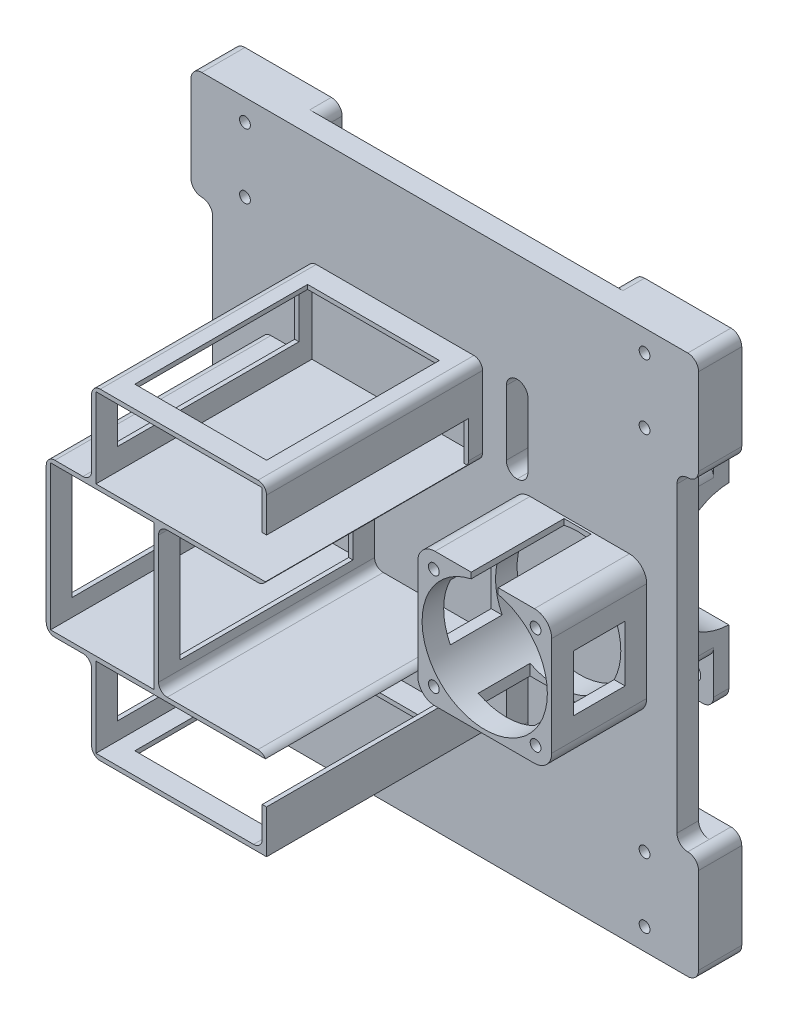
SolidWorks part; units mm, degrees
other "Marquage1"
sketch "Esquisse17" plane through (0, -52.2, -65) normal (-0.4358, -0.0146, -0.8999) x (-0.2736, 0.9547, 0.117)
ref_plane "Plan de face" through (0, 0, 0) normal (0, 0, 1) x (1, 0, 0)
ref_plane "Plan de dessus" through (0, 0, 0) normal (0, 1, 0) x (1, 0, 0)
ref_plane "Plan de droite" through (0, 0, 0) normal (1, 0, 0) x (0, 0, -1)
sketch "Esquisse1" plane through (0, 0, 0) normal (0, 0, 1) x (1, 0, 0)
  line L5 (235, 50) -> (235, 0)
  line L7 (0, 50) -> (0, 0)
  line L9 (235, 200) -> (235, 250)
  line L11 (0, 250) -> (0, 200)
  line L16 (225, 200) -> (225, 50)
  line L19 (146, 50) -> (156, 50)
  line L20 (225, 50) -> (235, 50)
  line L21 (225, 200) -> (235, 200)
  line L23 (10, 200) -> (10, 50)
  line L24 (0, 200) -> (10, 200)
  line L27 (10, 50) -> (0, 50)
  line L32 (0, 250) -> (235, 250)
  line L33 (0, 0) -> (235, 0)
  line L35 (146, 200) -> (156, 200)
  line L36 (146, 160) -> (156, 160)
  line L37 (146, 90) -> (156, 90)
  line L38 (146, 200) -> (146, 160)
  line L39 (156, 200) -> (156, 160)
  line L40 (146, 90) -> (146, 50)
  line L41 (156, 90) -> (156, 50)
  circle A0 centre (117.5, 125) radius 0.005
  dimension "D19" = 0.01
  dimension "D1" = 50
  dimension "D2" = 235
  dimension "D11" = 10
  dimension "D12" = 10
  dimension "D15" = 10
  dimension "D16" = 10
  dimension "D17" = 150
  dimension "D18" = 50
  dimension "D6" = 235
  dimension "D21" = 125
  dimension "D20" = 117.5
  dimension "D7" = 50
  dimension "D8" = 40
  dimension "D9" = 40
  dimension "D13" = 10
  dimension "D14" = 10
  dimension "D3" = 79
  dimension "D10" = 79
  dimension "D5" = 35
  dimension "D4" = 35
extrude "Boss.-Extru.2" add sketch "Esquisse1" along normal blind 10
sketch "Esquisse4" plane through (0, 0, 0) normal (0, 0, -1) x (-1, 0, 0)
  line L0 (0, 250) -> (0, 200) construction
  line L1 (0, 250) -> (-50, 250)
  line L2 (0, 250) -> (0, 200)
  line L4 (-50, 250) -> (-50, 200)
  line L5 (-117.5, 250) -> (-117.5, 0) construction
  line L6 (0, 0) -> (-235, 0) construction
  line L7 (-235, 200) -> (-185, 200)
  line L8 (-235, 250) -> (-235, 200)
  line L9 (-185, 250) -> (-185, 200)
  line L10 (-235, 250) -> (-185, 250)
  line L11 (-225, 125) -> (-10, 125) construction
  line L12 (-225, 50) -> (-225, 200) construction
  line L21 (-10, 200) -> (-10, 50) construction
  line L22 (0, 200) -> (-50, 200)
  line L24 (-235, 250) -> (0, 250) construction
  line L25 (0, 250) -> (0, 200) construction
  line L26 (-235, 50) -> (-185, 50)
  line L27 (-185, 0) -> (-185, 50)
  line L28 (-235, 0) -> (-235, 50)
  line L29 (-235, 0) -> (-185, 0)
  line L30 (0, 50) -> (-50, 50)
  line L31 (0, 0) -> (0, 50)
  line L32 (-50, 0) -> (-50, 50)
  line L33 (0, 0) -> (-50, 0)
  dimension "D1" = 50
  dimension "D2" = 50
extrude "Boss.-Extru.3" add sketch "Esquisse4" along normal blind 10
sketch "Esquisse6" plane through (0, 0, 0) normal (0, 0, -1) x (-1, 0, 0)
  line L0 (-225, 50) -> (-225, 200) construction
  line L1 (-126, 164) -> (-106, 164)
  line L2 (-126, 164) -> (-126, 86)
  line L3 (-126, 86) -> (-106, 86)
  line L4 (-106, 164) -> (-106, 86)
  line L5 (-146, 90) -> (-146, 50) construction
  line L6 (-50, 200) -> (0, 200) construction
  line L7 (-10, 50) -> (-50, 50) construction
  line L10 (-225, 200) -> (-185, 200) construction
  line L11 (-195, 164) -> (-175, 164)
  line L12 (-195, 164) -> (-195, 86)
  line L13 (-195, 86) -> (-175, 86)
  line L14 (-175, 164) -> (-175, 86)
  line L15 (-185, 50) -> (-225, 50) construction
  dimension "D5" = 36
  dimension "D6" = 36
  dimension "D1" = 20
  dimension "D8" = 30
  dimension "D3" = 36
  dimension "D4" = 36
  dimension "D7" = 50
  dimension "D2" = 20
extrude "Boss.-Extru.5" add sketch "Esquisse6" along normal blind 45
fillet "Congé1" radius 5 28 edges at (50, 250, -5) (50, 200, -5) (185, 250, -5) (185, 200, -5) (235, 50, 0) (235, 200, 0) (0, 50, 0) (0, 200, 0) (225, 50, 5) (225, 200, 5) (10, 50, 5) (10, 200, 5) (235, 250, 0) (0, 250, 0) (0, 0, 0) (235, 0, 0) (50, 50, -5) (185, 50, -5) (185, 0, -5) (50, 0, -5) (146, 50, 5) (156, 50, 5) (156, 90, 5) (146, 90, 5) (156, 160, 5) (146, 160, 5) (156, 200, 5) (146, 200, 5)
sketch "Esquisse8" plane through (195, 0, 0) normal (1, 0, 0) x (0, 0, -1)
  line L0 (22.5, 164) -> (22.5, 86) construction
  line L2 (45, 125) -> (-10, 125) construction
  line L3 (45, 164) -> (45, 86) construction
  line L4 (0, 164) -> (0, 86) construction
  line L5 (-10, 55) -> (-10, 195) construction
  line L6 (45, 164) -> (0, 164) construction
  line L7 (45, 86) -> (0, 86) construction
  circle A0 centre (45, 125) radius 28.5
  dimension "D1" = 45
  dimension "D2" = 57
extrude "Enlèv. mat.-Extru.2" cut sketch "Esquisse8" against normal blind 100
sketch "Esquisse12" plane through (0, 164, 0) normal (0, 1, 0) x (1, 0, 0)
  line L10 (126, 45) -> (126, 0) construction
  line L11 (106, 45) -> (126, 45)
  line L12 (106, 45) -> (106, 37)
  line L13 (106, 37) -> (126, 37)
  line L14 (126, 45) -> (126, 37)
  line L15 (195, 45) -> (195, 0) construction
  line L16 (175, 45) -> (195, 45)
  line L17 (175, 45) -> (175, 37)
  line L18 (175, 37) -> (195, 37)
  line L19 (195, 45) -> (195, 37)
  dimension "D1" = 8
  dimension "D2" = 8
extrude "Boss.-Extru.6" add sketch "Esquisse12" along normal blind 20
sketch "Esquisse13" plane through (0, 86, 0) normal (0, -1, 0) x (1, 0, 0)
  line L0 (126, -45) -> (126, 0) construction
  line L1 (106, -45) -> (126, -45)
  line L2 (106, -45) -> (106, -37)
  line L3 (106, -37) -> (126, -37)
  line L4 (126, -45) -> (126, -37)
  line L5 (195, -45) -> (195, 0) construction
  line L6 (175, -45) -> (195, -45)
  line L7 (175, -45) -> (175, -37)
  line L8 (175, -37) -> (195, -37)
  line L9 (195, -45) -> (195, -37)
  dimension "D1" = 8
  dimension "D2" = 8
extrude "Boss.-Extru.7" add sketch "Esquisse13" along normal blind 20
fillet "Congé55" radius 5 16 edges at (106, 184, -41) (175, 184, -41) (175, 66, -41) (106, 66, -41) (126, 66, -41) (195, 66, -41) (175, 164, -18.5) (195, 164, -18.5) (126, 164, -18.5) (106, 164, -18.5) (106, 86, -18.5) (126, 86, -18.5) (175, 86, -18.5) (195, 86, -18.5) (195, 184, -41) (126, 184, -41)
sketch "Esquisse14" plane through (0, 0, -45) normal (0, 0, -1) x (-1, 0, 0)
  line L0 (-175, 153.5) -> (-126, 153.5) construction
  line L1 (-150.5, 153.5) -> (-150.5, 184.1356) construction
  line L2 (-175, 153.5) -> (-175, 179) construction
  line L3 (-195, 125) -> (-106, 125) construction
  line L4 (-195, 159) -> (-195, 91) construction
  line L5 (-106, 91) -> (-106, 159) construction
  circle A0 centre (-185, 173.5) radius 4
  circle A1 centre (-116, 173.5) radius 4
  circle A2 centre (-116, 76.5) radius 4
  circle A3 centre (-185, 76.5) radius 4
  dimension "D1" = 8
  dimension "D2" = 20
  dimension "D3" = 10
extrude "Enlèv. mat.-Extru.4" cut sketch "Esquisse14" against normal blind 10
sketch "Esquisse15" plane through (0, 66, 0) normal (0, -1, 0) x (1, 0, 0)
  line L5 (195, -37) -> (195, -45) construction
  line L6 (175, -45) -> (195, -45)
  line L7 (175, -45) -> (175, -44)
  line L8 (175, -44) -> (195, -44)
  line L9 (195, -45) -> (195, -44)
  dimension "D1" = 1
extrude "Enlèv. mat.-Extru.5" cut sketch "Esquisse15" against normal blind 120
sketch "Esquisse19" plane through (0, 0, 10) normal (0, 0, 1) x (1, 0, 0)
  line L0 (117.5, 250) -> (117.5, -7.5909) construction
  line L1 (230, 250) -> (5, 250) construction
  line L2 (225, 125) -> (-27.1362, 125) construction
  line L3 (225, 55) -> (225, 195) construction
  line L5 (156, 165) -> (156, 195) construction
  line L6 (149, 94) -> (211, 94)
  line L7 (149, 94) -> (149, 156)
  line L8 (149, 156) -> (211, 156)
  line L9 (211, 94) -> (211, 156)
  line L10 (149, 94) -> (211, 156) construction
  line L11 (149, 156) -> (211, 94) construction
  line L12 (160, 105) -> (200, 105)
  line L13 (160, 105) -> (160, 145)
  line L14 (160, 145) -> (200, 145)
  line L15 (200, 105) -> (200, 145)
  line L16 (160, 105) -> (200, 145) construction
  line L17 (160, 145) -> (200, 105) construction
  point P8 (180, 125)
  point P11 (180, 125)
  dimension "D2" = 40
  dimension "D3" = 0
  dimension "D6" = 0
  dimension "D1" = 24
  dimension "D4" = 62
  dimension "D5" = 62
extrude "Boss.-Extru.8" add sketch "Esquisse19" along normal blind 44
sketch "Esquisse20" plane through (0, 0, 54) normal (0, 0, 1) x (1, 0, 0)
  line L0 (117.5, 250) -> (117.5, 0) construction
  line L1 (230, 250) -> (5, 250) construction
  line L2 (5, 0) -> (230, 0) construction
  line L3 (10, 125) -> (225, 125) construction
  line L4 (10, 195) -> (10, 55) construction
  line L5 (225, 55) -> (225, 195) construction
  line L6 (149, 156) -> (149, 94) construction
  circle A0 centre (180, 125) radius 29
  circle A1 centre (180, 125) radius 15
  point P12 (180, 125)
  dimension "D2" = 58
  dimension "D3" = 30
  dimension "D1" = 31
extrude "Enlèv. mat.-Extru.7" cut sketch "Esquisse20" against normal blind 44
fillet "Congé57" radius 8 4 edges at (211, 94, 32) (211, 156, 32) (149, 156, 32) (149, 94, 32)
sketch "Esquisse21" plane through (0, 0, 54) normal (0, 0, 1) x (1, 0, 0)
  line L0 (149, 148) -> (149, 102) construction
  line L1 (173.75, 158) -> (186.25, 158)
  line L2 (173.75, 158) -> (173.75, 152)
  line L3 (173.75, 152) -> (186.25, 152)
  line L4 (186.25, 158) -> (186.25, 152)
  line L7 (203, 156) -> (157, 156) construction
  point P6 (149, 125)
  point P9 (180, 156)
  dimension "D2" = 6
  dimension "D3" = 33
  dimension "D1" = 6.25
  dimension "D4" = 12.5
extrude "Enlèv. mat.-Extru.8" cut sketch "Esquisse21" against normal blind 43
sketch "Esquisse22" plane through (0, 0, 0) normal (0, 0, 1) x (1, 0, 0)
  line L0 (117.5, 250) -> (117.5, 0) construction
  line L1 (230, 250) -> (5, 250) construction
  line L2 (5, 0) -> (230, 0) construction
  line L3 (117.5, 0) -> (225, 125) construction
  line L4 (225, 55) -> (225, 195) construction
  line L5 (225, 125) -> (10, 125) construction
  line L6 (10, 195) -> (10, 55) construction
  line L7 (12.5, 240) -> (37.5, 240) construction
  line L8 (12.5, 245) -> (37.5, 245)
  line L9 (12.5, 235) -> (37.5, 235)
  line L10 (12.5, 210) -> (37.5, 210) construction
  line L11 (12.5, 215) -> (37.5, 215)
  line L12 (12.5, 205) -> (37.5, 205)
  line L13 (0, 245) -> (0, 205) construction
  line L16 (5, 200) -> (55.9669, 200) construction
  line L19 (12.5, 40) -> (37.5, 40) construction
  line L20 (12.5, 35) -> (37.5, 35)
  line L21 (12.5, 45) -> (37.5, 45)
  line L22 (12.5, 10) -> (37.5, 10) construction
  line L23 (12.5, 5) -> (37.5, 5)
  line L24 (12.5, 15) -> (37.5, 15)
  line L25 (222.5, 10) -> (197.5, 10) construction
  line L26 (222.5, 5) -> (197.5, 5)
  line L27 (222.5, 15) -> (197.5, 15)
  line L28 (222.5, 40) -> (197.5, 40) construction
  line L29 (222.5, 35) -> (197.5, 35)
  line L30 (222.5, 45) -> (197.5, 45)
  line L31 (222.5, 240) -> (197.5, 240) construction
  line L32 (222.5, 245) -> (197.5, 245)
  line L33 (222.5, 235) -> (197.5, 235)
  line L34 (222.5, 210) -> (197.5, 210) construction
  line L35 (222.5, 215) -> (197.5, 215)
  line L36 (222.5, 205) -> (197.5, 205)
  arc A0 (12.5, 245) -> (12.5, 235) centre (12.5, 240) ccw
  arc A1 (37.5, 235) -> (37.5, 245) centre (37.5, 240) ccw
  arc A2 (12.5, 215) -> (12.5, 205) centre (12.5, 210) ccw
  arc A3 (37.5, 205) -> (37.5, 215) centre (37.5, 210) ccw
  arc A8 (12.5, 35) -> (12.5, 45) centre (12.5, 40) cw
  arc A9 (37.5, 45) -> (37.5, 35) centre (37.5, 40) cw
  arc A10 (12.5, 5) -> (12.5, 15) centre (12.5, 10) cw
  arc A11 (37.5, 15) -> (37.5, 5) centre (37.5, 10) cw
  arc A12 (222.5, 5) -> (222.5, 15) centre (222.5, 10) ccw
  arc A13 (197.5, 15) -> (197.5, 5) centre (197.5, 10) ccw
  arc A14 (222.5, 35) -> (222.5, 45) centre (222.5, 40) ccw
  arc A15 (197.5, 45) -> (197.5, 35) centre (197.5, 40) ccw
  arc A16 (222.5, 245) -> (222.5, 235) centre (222.5, 240) cw
  arc A17 (197.5, 235) -> (197.5, 245) centre (197.5, 240) cw
  arc A18 (222.5, 215) -> (222.5, 205) centre (222.5, 210) cw
  arc A19 (197.5, 205) -> (197.5, 215) centre (197.5, 210) cw
  point P14 (25, 240)
  point P19 (25, 210)
  point P32 (25, 40)
  point P39 (25, 10)
  point P47 (210, 10)
  point P54 (210, 40)
  point P61 (210, 240)
  point P68 (210, 210)
  dimension "D3" = 5
  dimension "D4" = 5
  dimension "D1" = 25
  dimension "D2" = 25
  dimension "D5" = 25
  dimension "D6" = 25
  dimension "D7" = 10
  dimension "D8" = 10
extrude "Enlèv. mat.-Extru.9" cut sketch "Esquisse22" against normal blind 10
sketch "Esquisse23" plane through (0, 0, 0) normal (0, 0, 1) x (1, 0, 0)
  line L0 (117.5, 250) -> (117.5, 0) construction
  line L1 (230, 250) -> (5, 250) construction
  line L2 (5, 0) -> (230, 0) construction
  line L3 (117.5, 0) -> (225, 125) construction
  line L4 (225, 55) -> (225, 195) construction
  line L5 (225, 125) -> (10, 125) construction
  line L6 (10, 195) -> (10, 55) construction
  line L7 (0, 245) -> (0, 205) construction
  line L8 (5, 200) -> (40.2929, 200) construction
  circle A0 centre (25, 240) radius 2.5
  circle A1 centre (25, 210) radius 2.5
  circle A3 centre (25, 40) radius 2.5
  circle A4 centre (25, 10) radius 2.5
  circle A5 centre (210, 10) radius 2.5
  circle A6 centre (210, 40) radius 2.5
  circle A7 centre (210, 210) radius 2.5
  circle A8 centre (210, 240) radius 2.5
  dimension "D1" = 25
  dimension "D2" = 10
  dimension "D3" = 25
  dimension "D4" = 10
  dimension "D5" = 5
  dimension "D6" = 5
extrude "Enlèv. mat.-Extru.10" cut sketch "Esquisse23" along normal blind 10
sketch "Esquisse24" plane through (149, 0, 0) normal (-1, 0, 0) x (0, 0, 1)
  line L1 (20, 138) -> (44, 138)
  line L2 (20, 138) -> (20, 112)
  line L3 (20, 112) -> (44, 112)
  line L4 (44, 138) -> (44, 112)
  line L6 (54, 148) -> (54, 102) construction
  line L7 (10, 195) -> (10, 55) construction
  line L8 (54, 148) -> (10, 148) construction
  line L10 (10, 102) -> (54, 102) construction
  dimension "D3" = 10
  dimension "D4" = 10
  dimension "D1" = 10
  dimension "D2" = 10
extrude "Enlèv. mat.-Extru.11" cut sketch "Esquisse24" against normal mid plane 132
sketch "Esquisse25" plane through (0, 94, 0) normal (0, -1, 0) x (1, 0, 0)
  line L0 (157, 54) -> (203, 54) construction
  line L1 (167, 44) -> (193, 44)
  line L2 (167, 44) -> (167, 20)
  line L3 (167, 20) -> (193, 20)
  line L4 (193, 44) -> (193, 20)
  line L5 (203, 10) -> (203, 54) construction
  line L6 (157, 10) -> (203, 10) construction
  line L7 (157, 54) -> (157, 10) construction
  dimension "D1" = 10
  dimension "D2" = 10
  dimension "D3" = 10
  dimension "D4" = 10
extrude "Enlèv. mat.-Extru.12" cut sketch "Esquisse25" against normal blind 42
sketch "Esquisse27" plane through (0, 0, 10) normal (0, 0, 1) x (1, 0, 0)
  line L1 (135, 50.5) -> (54, 50.5)
  line L6 (117.5, 250) -> (117.5, 0) construction
  line L7 (230, 250) -> (5, 250) construction
  line L8 (5, 0) -> (230, 0) construction
  line L9 (10, 125) -> (225, 125) construction
  line L10 (10, 195) -> (10, 55) construction
  line L11 (225, 55) -> (225, 195) construction
  line L12 (54, 50.5) -> (54, 89.5)
  line L17 (135, 199.5) -> (54, 199.5)
  line L18 (54, 199.5) -> (54, 160.5)
  line L19 (54, 89.5) -> (33, 89.5)
  line L20 (33, 89.5) -> (33, 160.5)
  line L21 (33, 160.5) -> (54, 160.5)
  line L22 (135, 158.5) -> (85, 158.5)
  line L23 (85, 158.5) -> (85, 91.5)
  line L24 (85, 91.5) -> (135, 91.5)
  line L25 (135, 199.5) -> (135, 158.5)
  line L26 (135, 50.5) -> (135, 91.5)
  line L27 (146, 195) -> (146, 165) construction
  dimension "D1" = 81
  dimension "D2" = 149
  dimension "D3" = 11
  dimension "D4" = 71
  dimension "D5" = 33.5
  dimension "D6" = 50
  dimension "D7" = 21
  dimension "D8" = 33.5
extrude "Boss.-Extru.9" add sketch "Esquisse27" along normal blind 100
sketch "Esquisse31" plane through (0, 0, 110) normal (0, 0, 1) x (1, 0, 0)
  line L1 (56, 160.5) -> (133, 160.5)
  line L2 (56, 89.5) -> (133, 89.5)
  line L13 (133, 52.5) -> (56, 52.5)
  line L16 (56, 52.5) -> (56, 89.5)
  line L20 (56, 160.5) -> (56, 197.5)
  line L21 (56, 197.5) -> (133, 197.5)
  line L23 (135, 199.5) -> (54, 199.5) construction
  line L26 (54, 199.5) -> (54, 160.5) construction
  line L27 (133, 52.5) -> (133, 89.5)
  line L29 (54, 89.5) -> (54, 50.5) construction
  line L30 (133, 197.5) -> (133, 160.5)
  line L31 (35, 158.5) -> (35, 91.5)
  line L34 (54, 50.5) -> (135, 50.5) construction
  line L36 (35, 91.5) -> (83, 91.5)
  line L37 (83, 91.5) -> (83, 158.5)
  line L38 (83, 158.5) -> (35, 158.5)
  line L40 (33, 160.5) -> (33, 89.5) construction
  line L42 (135, 91.5) -> (85, 91.5) construction
  line L43 (85, 91.5) -> (85, 158.5) construction
  line L44 (85, 158.5) -> (135, 158.5) construction
  line L45 (135, 158.5) -> (135, 199.5) construction
  point P12 (109.5, 104.5)
  dimension "D1" = 2
  dimension "D2" = 0
  dimension "D3" = 2
  dimension "D4" = 77
  dimension "D5" = 2
  dimension "D6" = 0
  dimension "D7" = 2
  dimension "D8" = 2
  dimension "D9" = 2
  dimension "D10" = 2
  dimension "D11" = 2
  dimension "D12" = 2
extrude "Enlèv. mat.-Extru.17" cut sketch "Esquisse31" against normal blind 100
sketch "Esquisse35" plane through (0, 50.5, 0) normal (0, -1, 0) x (1, 0, 0)
  line L0 (54, 110) -> (135, 110) construction
  line L1 (64, 20) -> (125, 20)
  line L2 (64, 20) -> (64, 100)
  line L3 (64, 100) -> (125, 100)
  line L4 (125, 20) -> (125, 100)
  line L5 (135, 110) -> (135, 10) construction
  line L6 (5, 10) -> (230, 10) construction
  line L8 (54, 110) -> (54, 10) construction
  dimension "D1" = 10
  dimension "D2" = 10
  dimension "D3" = 10
  dimension "D4" = 10
extrude "Enlèv. mat.-Extru.20" cut sketch "Esquisse35" against normal blind 2
sketch "Esquisse36" plane through (54, 0, 0) normal (-1, 0, 0) x (0, 0, 1)
  line L0 (-32.165, 125) -> (116.1521, 125) construction
  line L2 (110, 199.5) -> (110, 160.5) construction
  line L3 (16, 170.5) -> (100, 170.5)
  line L4 (16, 170.5) -> (16, 189.5)
  line L5 (16, 189.5) -> (100, 189.5)
  line L6 (100, 170.5) -> (100, 189.5)
  line L7 (10, 199.5) -> (10, 160.5) construction
  line L8 (110, 199.5) -> (10, 199.5) construction
  line L14 (110, 160.5) -> (10, 160.5) construction
  line L19 (110, 89.5) -> (10, 89.5) construction
  line L25 (110, 50.5) -> (10, 50.5) construction
  line L26 (16, 60.5) -> (100, 60.5)
  line L27 (16, 60.5) -> (16, 79.5)
  line L28 (16, 79.5) -> (100, 79.5)
  line L29 (100, 60.5) -> (100, 79.5)
  line L30 (110, 89.5) -> (110, 50.5) construction
  line L32 (10, 89.5) -> (10, 50.5) construction
  dimension "D2" = 6
  dimension "D1" = 10
  dimension "D3" = 10
  dimension "D5" = 10
  dimension "D6" = 10
  dimension "D8" = 6
  dimension "D4" = 10
  dimension "D7" = 10
extrude "Enlèv. mat.-Extru.26" cut sketch "Esquisse36" against normal blind 2
sketch "Esquisse37" plane through (33, 0, 0) normal (-1, 0, 0) x (0, 0, 1)
  line L0 (-31.1815, 125) -> (105.2441, 125) construction
  line L2 (20, 150.5) -> (100, 150.5)
  line L3 (20, 150.5) -> (20, 99.5)
  line L4 (20, 99.5) -> (100, 99.5)
  line L5 (100, 150.5) -> (100, 99.5)
  line L9 (10, 160.5) -> (10, 89.5) construction
  line L10 (110, 160.5) -> (10, 160.5) construction
  line L11 (110, 160.5) -> (110, 89.5) construction
  line L12 (110, 89.5) -> (10, 89.5) construction
  dimension "D1" = 10
  dimension "D2" = 10
  dimension "D3" = 10
  dimension "D4" = 10
extrude "Enlèv. mat.-Extru.22" cut sketch "Esquisse37" against normal blind 52
fillet "Congé58" radius 4 12 edges at (54, 199.5, 60) (54, 50.5, 60) (135, 91.5, 60) (133, 52.5, 60) (135, 199.5, 60) (135, 158.5, 60) (33, 160.5, 60) (33, 89.5, 60) (54, 160.5, 60) (85, 158.5, 60) (85, 91.5, 60) (54, 89.5, 60)
sketch "Esquisse38" plane through (0, 199.5, 0) normal (0, 1, 0) x (1, 0, 0)
  line L0 (230, -10) -> (5, -10) construction
  line L1 (64, -100) -> (125, -100)
  line L2 (64, -100) -> (64, -20)
  line L3 (64, -20) -> (125, -20)
  line L4 (125, -100) -> (125, -20)
  line L5 (135, -10) -> (135, -110) construction
  line L6 (131, -110) -> (58, -110) construction
  line L8 (54, -110) -> (54, -10) construction
  dimension "D1" = 10
  dimension "D2" = 10
  dimension "D3" = 10
  dimension "D4" = 10
extrude "Enlèv. mat.-Extru.23" cut sketch "Esquisse38" against normal blind 2
sketch "Esquisse39" plane through (135, 0, 0) normal (1, 0, 0) x (0, 0, -1)
  line L0 (-110, 199.5) -> (-10, 199.5) construction
  line L14 (-110, 179.5) -> (-16.5, 179.5)
  line L15 (-110, 179.5) -> (-110, 160.5)
  line L16 (-110, 160.5) -> (-16.5, 160.5)
  line L17 (-16.5, 179.5) -> (-16.5, 160.5)
  line L20 (-10, 160.5) -> (-110, 160.5) construction
  line L21 (-110, 89.5) -> (-30, 89.5)
  line L22 (-110, 89.5) -> (-110, 70.5)
  line L23 (-110, 70.5) -> (-30, 70.5)
  line L24 (-30, 89.5) -> (-30, 70.5)
  line L25 (-10, 55) -> (-10, 195) construction
  line L26 (-110, 162.5) -> (-110, 195.5) construction
  line L27 (-110, 50.5) -> (-10, 50.5) construction
  line L29 (-110, 50.5) -> (-110, 87.5) construction
  point P7 (-110, 179)
  point P8 (-110, 179.5)
  point P9 (-110, 70.5)
  point P24 (-110, 89.5)
  dimension "D4" = 0
  dimension "D7" = 20
  dimension "D1" = 6.5
  dimension "D2" = 20
  dimension "D3" = 20
extrude "Enlèv. mat.-Extru.24" cut sketch "Esquisse39" against normal blind 2
sketch "Esquisse42" plane through (0, 0, 54) normal (0, 0, 1) x (1, 0, 0)
  line L0 (180, 156) -> (180, 94) construction
  line L1 (186.25, 156) -> (173.75, 156) construction
  line L2 (157, 94) -> (203, 94) construction
  line L3 (149, 125) -> (211, 125) construction
  line L4 (149, 148) -> (149, 102) construction
  line L5 (211, 102) -> (211, 148) construction
  circle A0 centre (156.45, 148.55) radius 2.5
  circle A1 centre (203.55, 148.55) radius 2.5
  circle A2 centre (203.55, 101.45) radius 2.5
  circle A3 centre (156.45, 101.45) radius 2.5
  dimension "D3" = 5
  dimension "D1" = 7.45
  dimension "D2" = 7.45
extrude "Enlèv. mat.-Extru.29" cut sketch "Esquisse42" against normal blind 10
sketch "Esquisse43" plane through (106, 0, 0) normal (-1, 0, 0) x (0, 0, 1)
  line L0 (0, 91) -> (0, 159) construction
  line L1 (0, 159) -> (-37, 159) construction
  line L2 (0, 125) -> (-10.1633, 125) construction
  circle A0 centre (-21.47, 148.53) radius 2.6
  circle A1 centre (-21.47, 101.47) radius 2.6
  dimension "D2" = 5.2
  dimension "D1" = 21.47
  dimension "D3" = 10.47
extrude "Enlèv. mat.-Extru.30" cut sketch "Esquisse43" against normal blind 20
equation "\"D15@Esquisse1\"=\"D11@Esquisse1\""
equation "\"D16@Esquisse1\"=\"D12@Esquisse1\""
equation "\"D18@Esquisse1\"=\"D1@Esquisse1\""
equation "\"D12@Esquisse1\"=\"D11@Esquisse1\""
equation "\"D5@Esquisse6\"=\"D3@Esquisse6\""
equation "\"D6@Esquisse6\"=\"D3@Esquisse6\""
equation "\"D2@Esquisse13\"=\"D1@Esquisse13\""
equation "\"D2@Esquisse12\"=\"D1@Esquisse12\""
equation "\"D21@Esquisse1\"=(\"D1@Esquisse1\"+\"D17@Esquisse1\"+\"D7@Esquisse1\")/2"
equation "\"D6@Esquisse1\"=\"D2@Esquisse1\""
equation "\"D20@Esquisse1\"=\"D2@Esquisse1\"/2"
equation "\"D2@Esquisse4\"=\"D1@Esquisse4\""
equation "\"D7@Esquisse1\"=\"D1@Esquisse1\""
equation "\"D4@Esquisse6\"=\"D3@Esquisse6\""
equation "\"D1@Esquisse21\"=\"D4@Esquisse21\"/2"
equation "\"D2@Esquisse36\"=6"
equation "\"D5@Esquisse36\"=\"D4@Esquisse36\""
equation "\"D6@Esquisse36\"=\"D1@Esquisse36\""
equation "\"D8@Esquisse36\"=\"D2@Esquisse36\""
equation "\"D7@Esquisse39\"=\"D2@Esquisse39\""
equation "\"D5@Esquisse39\"=\"D4@Esquisse39\""
equation "\"D9@Esquisse1\"=\"D8@Esquisse1\""
equation "\"D14@Esquisse1\"=\"D13@Esquisse1\""
equation "\"D2@Esquisse24\"=\"D1@Esquisse24\""
equation "\"D3@Esquisse24\"=\"D4@Esquisse24\""
equation "\"D10@Esquisse1\"=\"D3@Esquisse1\""
equation "\"D4@Esquisse1\"=\"D5@Esquisse1\""
equation "\"D3@Esquisse43\"=(13.07-(5.2/2))"
equation "\"D1@Esquisse43\"=24.07-(5.2/2)"
